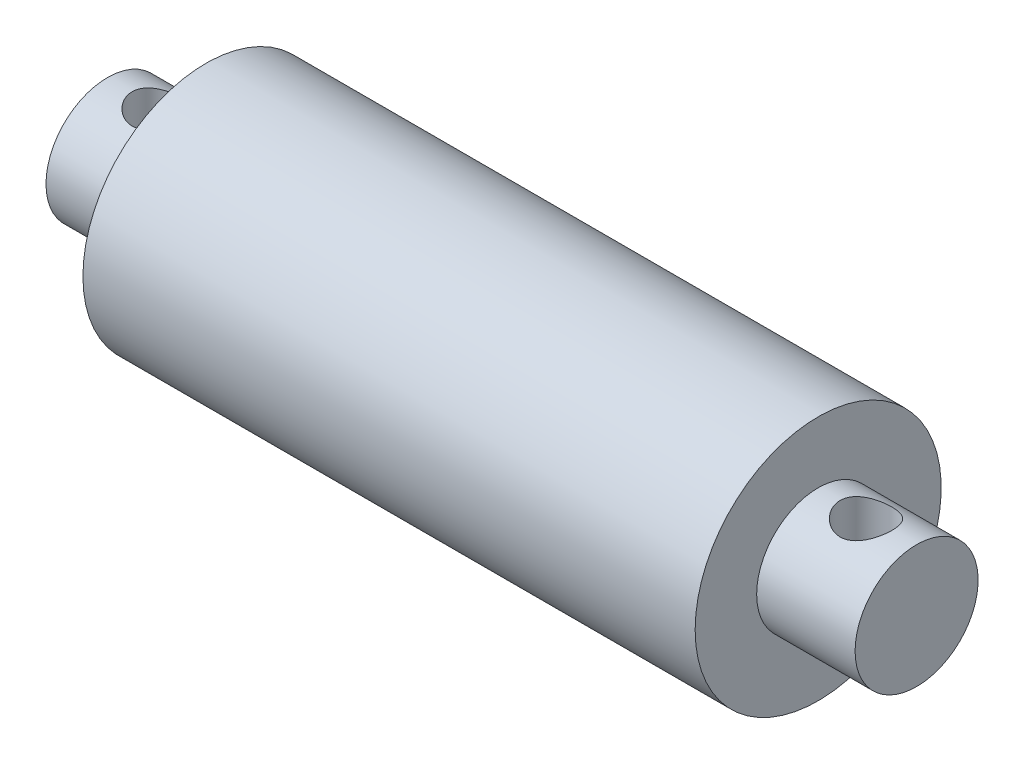
SolidWorks part; units mm, degrees
ref_plane "Front Plane" through (0, 0, 0) normal (0, 0, 1) x (1, 0, 0)
ref_plane "Top Plane" through (0, 0, 0) normal (0, 1, 0) x (1, 0, 0)
ref_plane "Right Plane" through (0, 0, 0) normal (1, 0, 0) x (0, 0, -1)
sketch "Sketch1" plane through (0, 0, 0) normal (0, 0, 1) x (1, 0, 0)
  line L0 (0, 0) -> (50, 0)
  line L1 (49.7614, 5) -> (49.7614, 10)
  line L2 (49.7614, 10) -> (0, 10)
  line L3 (0, 10) -> (0, 5)
  line L4 (50, 0) -> (57.7614, 0)
  line L5 (57.7614, 0) -> (57.7614, 5)
  line L6 (57.7614, 5) -> (49.7614, 5)
  line L8 (0, 5) -> (-8, 5)
  line L9 (-8, 5) -> (-8, 0)
  line L10 (-8, 0) -> (0, 0)
  dimension "D1" = 10
  dimension "D2" = 50
  dimension "D3" = 5
  dimension "D4" = 8
  dimension "D5" = 8
  dimension "D6" = 5
revolve "Revolve1" add sketch "Sketch1" angle 360 about L0
sketch "Sketch2" plane through (0, 0, 0) normal (0, 1, 0) x (1, 0, 0)
  circle A0 centre (-4, 0) radius 2
  circle A1 centre (53.6522, 0) radius 2.108
  point P0 (53.6522, 0)
extrude "Cut-Extrude1" cut sketch "Sketch2" along normal blind 10 and the other way blind 10
